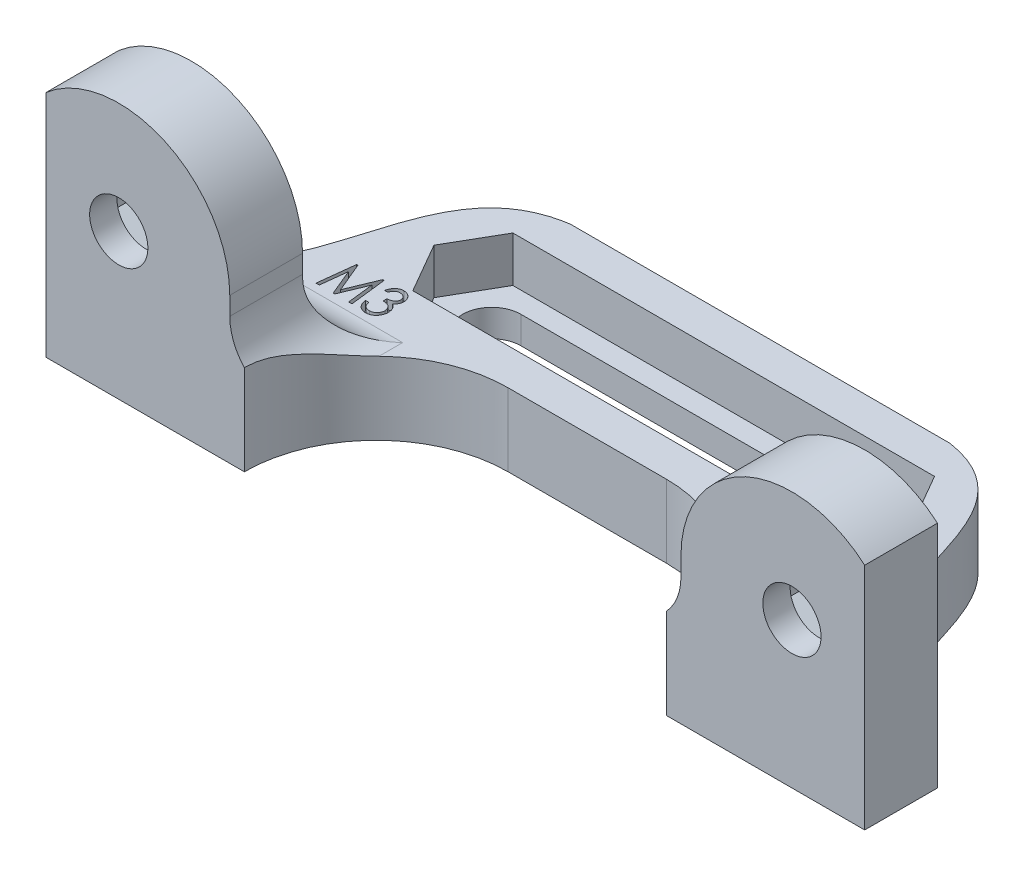
SolidWorks part; units mm, degrees
material "ABS"
ref_plane "Front Plane" through (0, 0, 0) normal (0, 0, 1) x (1, 0, 0)
ref_plane "Top Plane" through (0, 0, 0) normal (0, 1, 0) x (1, 0, 0)
ref_plane "Right Plane" through (0, 0, 0) normal (1, 0, 0) x (0, 0, -1)
other "Configuration Table"
sketch "Sketch1" plane through (0, 0, 0) normal (1, 0, 0) x (0, 0, -1)
  line L0 (0, 15) -> (0, 0)
  line L3 (0, 15) -> (4, 15)
  line L4 (4, 4) -> (4, 15)
  line L5 (0, 0) -> (20, 0)
  line L7 (4, 4) -> (20, 4)
  line L8 (20, 0) -> (20, 4)
  dimension "D1" = 4
  dimension "D2" = 4
  dimension "D3" = 15
  dimension "D4" = 20
extrude "Boss-Extrude1" add sketch "Sketch1" along normal mid plane 45
sketch "Sketch4" plane through (0, 0, 0) normal (0, 0, 1) x (1, 0, 0)
  line L0 (0, 0) -> (0, 15) construction
  line L1 (22.5, 15) -> (-22.5, 15) construction
  line L3 (22.5, 4) -> (-22.5, 4) construction
  circle A0 centre (-18.5, 8) radius 1.6
  circle A1 centre (18.5, 8) radius 1.6
  dimension "D1" = 3.2
  dimension "D3" = 4
  dimension "D2" = 37
extrude "Hole-Sharp" cut sketch "Sketch4" against normal through all
sketch "Sketch5" plane through (0, 0, -4) normal (0, 0, -1) x (-1, 0, 0)
  line L0 (-22.5, 4) -> (-22.5, 15) construction
  line L1 (-15.75, 6.4123) -> (-15.75, 9.5877)
  line L2 (-15.75, 9.5877) -> (-18.5, 11.1754)
  line L3 (-18.5, 11.1754) -> (-21.25, 9.5877)
  line L4 (-21.25, 9.5877) -> (-21.25, 6.4123)
  line L5 (-21.25, 6.4123) -> (-18.5, 4.8246)
  line L6 (-18.5, 4.8246) -> (-15.75, 6.4123)
  line L7 (18.5, 4.8246) -> (21.25, 6.4123)
  line L8 (21.25, 6.4123) -> (21.25, 9.5877)
  line L9 (21.25, 9.5877) -> (18.5, 11.1754)
  line L10 (18.5, 11.1754) -> (15.75, 9.5877)
  line L11 (15.75, 9.5877) -> (15.75, 6.4123)
  line L12 (15.75, 6.4123) -> (18.5, 4.8246)
  circle A0 centre (-18.5, 8) radius 2.75 construction
  circle A1 centre (18.5, 8) radius 2.75 construction
  dimension "D1" = 5.5
extrude "Pocket-SharpNuts" cut sketch "Sketch5" against normal offset from surface (2.5 mm away) 1.5 up to face at (-16.9, 8, 0)
sketch "Sketch8" plane through (0, 0, 0) normal (0, 1, 0) x (1, 0, 0)
  line L0 (0, 0) -> (0, 20) construction
  line L1 (22.5, 0) -> (-22.5, 0) construction
  line L2 (22.5, 20) -> (-22.5, 20) construction
  line L4 (-10, 13.6) -> (10, 13.6)
  line L6 (-10, 10.4) -> (10, 10.4)
  arc A0 (-10, 13.6) -> (-10, 10.4) centre (-10, 12) ccw
  arc A1 (10, 13.6) -> (10, 10.4) centre (10, 12) cw
  dimension "D3" = 3.2
  dimension "D1" = 8
  dimension "D2" = 20
extrude "Hole-mount" cut sketch "Sketch8" along normal through all
sketch "Sketch6" plane through (0, 0, 0) normal (0, 1, 0) x (1, 0, 0)
  line L0 (-10, 12) -> (10, 12) construction
  line L1 (0, 0) -> (0, 20) construction
  line L2 (22.5, 0) -> (-22.5, 0) construction
  line L3 (22.5, 20) -> (-22.5, 20) construction
  line L20 (8.4123, 9.25) -> (6.8246, 12) construction
  line L21 (-6.8246, 12) -> (-8.4123, 14.75) construction
  line L22 (-8.4123, 14.75) -> (-11.5877, 14.75)
  line L23 (-11.5877, 14.75) -> (-13.1754, 12)
  line L24 (-13.1754, 12) -> (-11.5877, 9.25)
  line L25 (-11.5877, 9.25) -> (-8.4123, 9.25)
  line L26 (-8.4123, 9.25) -> (-6.8246, 12) construction
  line L27 (11.5877, 9.25) -> (8.4123, 9.25)
  line L28 (13.1754, 12) -> (11.5877, 9.25)
  line L29 (11.5877, 14.75) -> (13.1754, 12)
  line L30 (8.4123, 14.75) -> (11.5877, 14.75)
  line L31 (6.8246, 12) -> (8.4123, 14.75) construction
  line L32 (-8.4123, 14.75) -> (8.4123, 14.75)
  line L33 (8.4123, 9.25) -> (-8.4123, 9.25)
  line L34 (10, 13.6) -> (-10, 13.6) construction
  line L35 (-10, 10.4) -> (10, 10.4) construction
  circle A0 centre (-10, 12) radius 2.75 construction
  circle A1 centre (10, 12) radius 2.75 construction
  dimension "D1" = 5.5
  dimension "D2" = 20
extrude "Slot-Nuts" cut sketch "Sketch6" against normal offset from surface (2.5 mm away) 1.5 from surface up to face at (0, 0, -10) starting at face at (0, 4, -12)
sketch "Sketch9" plane through (0, 0, 0) normal (0, 0, 1) x (1, 0, 0)
  line L1 (0, 0) -> (0, 15) construction
  line L2 (22.5, 15) -> (-22.5, 15) construction
  line L3 (22.5, 0) -> (-22.5, 0) construction
  line L4 (-2.5, 2) -> (2.5, 2)
  line L5 (-2.5, 2) -> (-2.5, 0)
  line L6 (-2.5, 0) -> (2.5, 0)
  line L7 (2.5, 2) -> (2.5, 0)
  line L8 (-2.5, 2) -> (2.5, 0) construction
  line L9 (-2.5, 0) -> (2.5, 2) construction
  point P4 (0, 1)
  dimension "D1" = 5
  dimension "D2" = 2
extrude "channel-wires" [suppressed] cut sketch "Sketch9" against normal through all
fillet "fill-stiffener" radius 2.5 1 edges at (0, 4, -4)
ref_plane "SLOT-SHARP" through (0, 0, -12) normal (0, 0, -1) x (-1, 0, 0)
sketch "Sketch10" plane through (0, 0, 0) normal (0, 1, 0) x (1, 0, 0)
  line L0 (0, 0) -> (0, 20) construction
  line L1 (22.5, 20) -> (-22.5, 20) construction
  line L2 (-10.433, 16.75) -> (10.433, 16.75)
  line L3 (-11.5877, 9.25) -> (11.5877, 9.25) construction
  line L4 (11.5877, 14.75) -> (-11.5877, 14.75) construction
  line L5 (-11.5877, 14.75) -> (-13.1754, 12) construction
  line L6 (-22.5, 4) -> (-22.5, 20)
  line L7 (-22.5, 20) -> (22.5, 20)
  line L8 (22.5, 20) -> (22.5, 4)
  line L9 (22.5, 4) -> (-22.5, 4) construction
  spline S0 degree 3 poles (-22.5, 4) (-13.2971, 4.2849) (-17.9401, 15.6125) (-10.433, 16.75) knots 0 0 0 0 1 1 1 1
  spline S1 degree 3 poles (22.5, 4) (13.2971, 4.2849) (17.9401, 15.6125) (10.433, 16.75) knots 0 0 0 0 1 1 1 1
  point P25 (0, 16.75)
  dimension "D1" = 2
  dimension "D2" = 2
  dimension "D3" = 4.5
extrude "board-contour" cut sketch "Sketch10" along normal through all
sketch "Sketch11" plane through (0, 0, 0) normal (0, 1, 0) x (1, 0, 0)
  line L0 (22.5, 0) -> (-22.5, 0) construction
  line L1 (11.6, 0) -> (-11.6, 0)
  line L2 (0, 0) -> (0, 16.75) construction
  line L3 (-10.433, 16.75) -> (10.433, 16.75) construction
  line L4 (-11.6, 12) -> (-11.6, 0) construction
  line L5 (-11.5877, 9.25) -> (11.5877, 9.25) construction
  line L6 (-4.35, 7.25) -> (4.35, 7.25)
  arc A0 (-4.35, 7.25) -> (-11.6, 0) centre (-4.35, 0) ccw
  arc A1 (-10, 13.6) -> (-10, 10.4) centre (-10, 12) ccw construction
  arc A2 (4.35, 7.25) -> (11.6, 0) centre (4.35, 0) cw
  point P24 (0, 7.25)
  dimension "D1" = 2
extrude "board-innercountour" cut sketch "Sketch11" along normal through all
sketch "Sketch14" plane through (0, 0, 0) normal (0, 0, 1) x (1, 0, 0)
  line L1 (-22.5, 12.6054) -> (-22.5, 15)
  line L4 (-22.5, 15) -> (-22.5, 0) construction
  line L8 (0, 0) -> (0, 15) construction
  line L13 (-12.4, 8) -> (-12.4, 7)
  line L35 (-22.5, 15) -> (22.5, 15)
  line L37 (-9.4, 4) -> (9.4, 4)
  line L40 (22.5, 15) -> (11.6, 15) construction
  line L41 (12.4, 8) -> (12.4, 7)
  line L42 (22.5, 12.6054) -> (22.5, 15)
  arc A0 (-12.4, 8) -> (-22.5, 12.6054) centre (-18.5, 8) ccw
  circle A4 centre (-18.5, 8) radius 1.6 construction
  arc A5 (-9.4, 4) -> (-12.4, 7) centre (-9.4, 7) cw
  arc A6 (9.4, 4) -> (12.4, 7) centre (9.4, 7) ccw
  arc A7 (12.4, 8) -> (22.5, 12.6054) centre (18.5, 8) cw
  dimension "D1" = 4.5
  dimension "D2" = 3
extrude "sharp-cutout" cut sketch "Sketch14" against normal through all
sketch "Sketch15" plane through (0, 4, 0) normal (0, 1, 0) x (1, 0, 0)
  text T0 "M3" font "Century Gothic" height 2
extrude "size-M3" cut sketch "Sketch15" against normal blind 0.5
